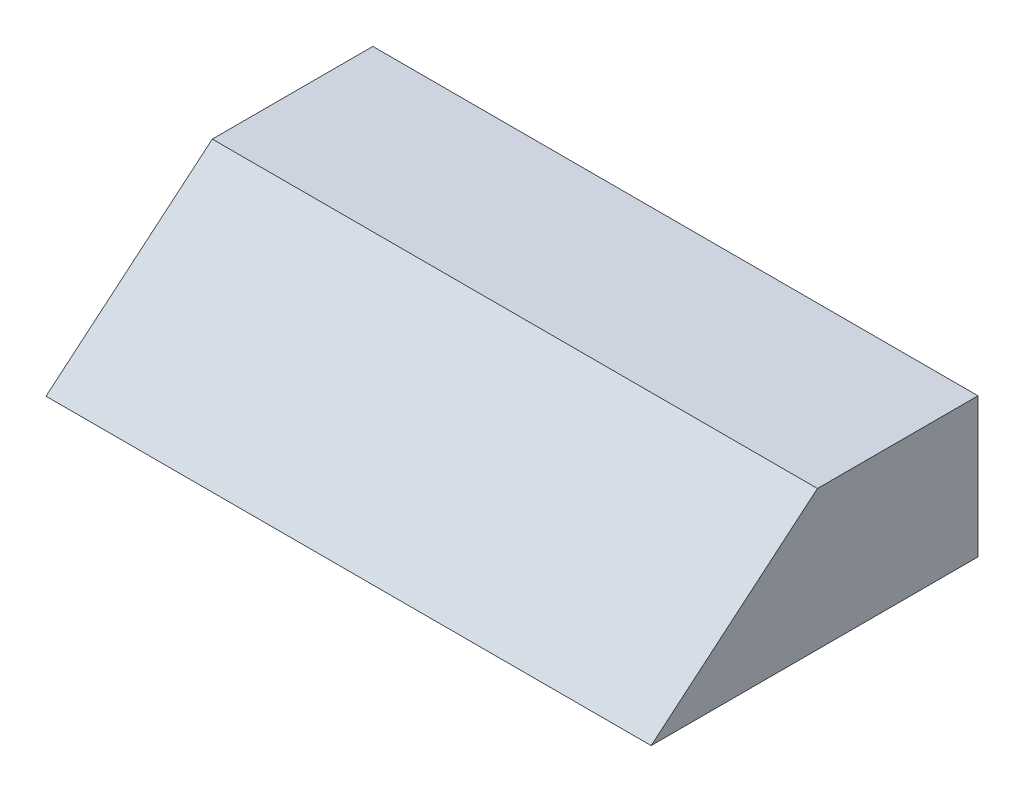
SolidWorks part; units mm, degrees
ref_plane "Alzado" through (0, 0, 0) normal (0, 0, 1) x (1, 0, 0)
ref_plane "Planta" through (0, 0, 0) normal (0, 1, 0) x (1, 0, 0)
ref_plane "Vista lateral" through (0, 0, 0) normal (1, 0, 0) x (0, 0, -1)
sketch "Croquis1" plane through (0, 0, 0) normal (1, 0, 0) x (0, 0, -1)
  line L0 (0, 0) -> (105.85, 0)
  line L1 (105.85, 0) -> (105.85, 45.19)
  line L2 (105.85, 45.19) -> (53.8553, 45.19)
  line L3 (0, 0) -> (53.8553, 45.19)
  line L4 (105.8531, 0) -> (105.8531, 45.19) construction
  line L5 (105.85, 0) -> (0, 0) construction
  line L6 (53.8553, 45.19) -> (168.8353, 45.19) construction
  dimension "D1" = 105.85
  dimension "D2" = 45.19
  dimension "D3" = 140
extrude "Saliente-Extruir1" add sketch "Croquis1" along normal blind 196
shell "Vaciado1" thickness 4 removed face at (98, 0, -52.925)
